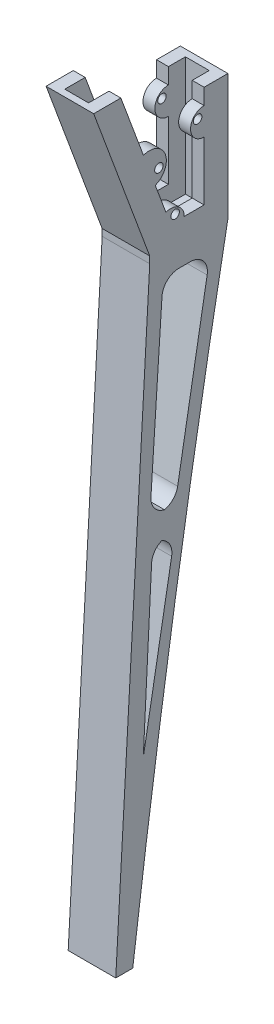
SolidWorks part; units mm, degrees
ref_plane "Front Plane" through (0, 0, 0) normal (0, 0, 1) x (1, 0, 0)
ref_plane "Top Plane" through (0, 0, 0) normal (0, 1, 0) x (1, 0, 0)
ref_plane "Right Plane" through (0, 0, 0) normal (1, 0, 0) x (0, 0, -1)
sketch "Sketch1" plane through (0, 0, 0) normal (0, 1, 0) x (1, 0, 0)
  line L0 (7, 0) -> (10.5, 0)
  line L2 (0, 0) -> (0, 5)
  line L3 (0, 5) -> (7, 5)
  line L4 (7, 0) -> (7, 5)
  line L5 (-3.5, 0) -> (0, 0)
  line L6 (-3.5, 0) -> (-3.5, 7)
  line L7 (-3.5, 7) -> (10.5, 7)
  line L8 (10.5, 0) -> (10.5, 7)
  dimension "D1" = 5
  dimension "D2" = 7
  dimension "D3" = 14
  dimension "D4" = 7
  dimension "D6" = 3.5
extrude "Boss-Extrude1" add sketch "Sketch1" along normal blind 35
sketch "Sketch6" plane through (0, 0, 0) normal (0, -1, 0) x (1, 0, 0)
  line L1 (10.5, -7) -> (-3.5, -7)
  line L2 (10.5, -7) -> (10.5, 16)
  line L3 (10.5, 16) -> (-3.5, 16)
  line L4 (-3.5, -7) -> (-3.5, 16)
  dimension "D1" = 14
  dimension "D2" = 23
extrude "Boss-Extrude6" add sketch "Sketch6" along normal blind 2
sketch "Sketch7" plane through (0, 0, 0) normal (0, 1, 0) x (1, 0, 0)
  line L0 (-3.5, -16) -> (10.5, -16)
  line L1 (10.5, -16) -> (10.5, -8)
  line L2 (10.5, 0) -> (10.5, -16) construction
  line L3 (10.5, -8) -> (7, -8)
  line L4 (7, -8) -> (7, -14)
  line L5 (7, -14) -> (0, -14)
  line L6 (0, -14) -> (0, -8)
  line L7 (0, -8) -> (-3.5, -8)
  line L8 (-3.5, -16) -> (-3.5, 0) construction
  line L9 (-3.5, -8) -> (-3.5, -16)
  dimension "D1" = 2
  dimension "D2" = 8
  dimension "D3" = 7
sketch "Sketch8" plane through (10.5, 0, 0) normal (1, 0, 0) x (0, 0, -1)
  line L2 (-32.5, 44.5) -> (-16, 0)
  dimension "D1" = 16.5
  dimension "D2" = 44.5
sweep "Sweep1" add profiles "Sketch7" path "Sketch8"
sketch "Sketch9" plane through (10.5, 0, 0) normal (1, 0, 0) x (0, 0, -1)
  line L0 (-16, -2) -> (-26, -179)
  line L1 (-16, -2) -> (7, -2)
  line L4 (-5.0833, -7.4335) -> (-12.0833, -7.4335)
  line L5 (-26, -179) -> (-21, -179)
  line L6 (-12.0833, -7.4335) -> (-16, -66.9304)
  line L7 (-5.0833, -7.4335) -> (1.9167, -7.4335)
  line L8 (1.9167, -7.4335) -> (-8.5141, -66.9304)
  line L9 (-8.5141, -66.9304) -> (-16, -66.9304)
  line L10 (-12.2153, -73.8738) -> (-15.2153, -73.8738)
  line L11 (-15.2153, -73.8738) -> (-17.9029, -126.8584)
  line L12 (-17.9029, -126.8584) -> (-8.5141, -73.8738)
  line L13 (-8.5141, -73.8738) -> (-12.2153, -73.8738)
  spline S1 degree 2 poles (7, -2) (-9.6602, -89.8354) (-21, -179) knots 0 0 0 0.8965 0.8965 0.8965
  dimension "D1" = 177
  dimension "D2" = 5
  dimension "D3" = 10
sketch "Sketch13" plane through (10.5, 0, 0) normal (1, 0, 0) x (0, 0, -1)
  line L0 (-8, 0) -> (0, 0)
  line L1 (0, 0) -> (0, 5)
  line L2 (0, 35) -> (0, 0) construction
  line L3 (0, 5) -> (-9.8539, 5)
  line L4 (-24.5, 44.5) -> (-8, 0) construction
  line L5 (-9.8539, 5) -> (-8, 0)
extrude "Boss-Extrude8" add sketch "Sketch13" against normal up to surface (3.5 mm away) up to face at (7, 22.25, 19.25)
sketch "Sketch14" plane through (10.5, 0, 0) normal (1, 0, 0) x (0, 0, -1)
  line L0 (-9.8539, 5) -> (-11.2435, 8.7476)
  line L1 (-24.5, 44.5) -> (-9.8539, 5) construction
  line L2 (-9.8539, 5) -> (-5.8571, 5)
  arc A0 (-5.8571, 5) -> (-11.2435, 8.7476) centre (-9.8539, 5) ccw
  circle A1 centre (-8.532, 6.9) radius 1.25
  dimension "D1" = 1.9
  dimension "D2" = 1.9
extrude "Boss-Extrude9" add sketch "Sketch14" against normal up to surface (14 mm away) up to face at (-3.5, 21.6389, 10.5833)
sketch "Sketch15" plane through (-3.5, 0, 0) normal (-1, 0, 0) x (0, 0, 1)
  line L0 (0, 0) -> (8, 0)
  line L1 (8, 0) -> (9.8539, 5)
  line L2 (9.8539, 5) -> (0, 5)
  line L3 (0, 35) -> (0, 0) construction
  line L4 (0, 5) -> (0, 0)
extrude "Boss-Extrude10" add sketch "Sketch15" against normal up to surface (3.5 mm away) up to face at (0, 17.5, -2.5)
sketch "Sketch16" plane through (10.5, 0, 0) normal (1, 0, 0) x (0, 0, -1)
  line L0 (0, 5) -> (0, 26.3175)
  line L1 (0, 35) -> (0, 5) construction
  line L2 (0, 30.3175) -> (0, 22.3175)
  arc A0 (0, 30.3175) -> (0, 22.3175) centre (0, 26.3175) ccw
  circle A1 centre (-1.9, 27.8175) radius 1.25
  line M1 (0, 35) -> (0, 5)
  dimension "D1" = 1.9
  dimension "D2" = 5.5
extrude "Boss-Extrude11" add sketch "Sketch16" against normal up to surface (14 mm away) contours A0 A1 M1 region at (10.5, 25.9534, 1.6485) up to face at (-3.5, 20.8031, 9.775)
sketch "Sketch18" plane through (10.5, 0, 0) normal (1, 0, 0) x (0, 0, -1)
  line L1 (-24.5, 44.5) -> (-11.2435, 8.7476) construction
  line L3 (-14.3724, 17.1861) -> (-17.8717, 26.6238)
  arc A0 (-14.3724, 17.1861) -> (-17.849, 26.5624) centre (-16.1107, 21.8743) ccw
  circle A1 centre (-13.3107, 21.0743) radius 1.25
  line M6 (-11.2435, 8.7476) -> (-24.5, 44.5)
  dimension "D1" = 0.8
  dimension "D4" = 5
  dimension "D2" = 2.8
  dimension "D3" = 14
extrude "Boss-Extrude12" add sketch "Sketch18" against normal up to surface (14 mm away) contours A0 A1 M6 region at (10.5, 22.8317, 14.2367) up to face at (-3.5, 21.3888, 8.4791)
sketch "Sketch19" plane through (0, 0, 0) normal (0, 1, 0) x (1, 0, 0)
  line L1 (0, -14) -> (7, -14)
  line L2 (0, -14) -> (0, 5)
  line L3 (0, 5) -> (7, 5)
  line L4 (7, -14) -> (7, 5)
extrude "Cut-Extrude5" cut sketch "Sketch19" along normal through all
sketch "Sketch20" plane through (0, -4.5636, 12.3079) normal (0, 0.3477, -0.9376) x (-1, 0, 0)
  line L1 (0, 52.3277) -> (-7, 52.3277)
  line L2 (0, 52.3277) -> (0, 4.8672)
  line L3 (0, 4.8672) -> (-7, 4.8672)
  line L4 (-7, 52.3277) -> (-7, 4.8672)
extrude "Cut-Extrude6" cut sketch "Sketch20" along normal blind 10
extrude "Boss-Extrude13" add sketch "Sketch9" against normal up to surface (14 mm away) up to face at (-3.5, 21.2475, 9.1103)
fillet "Fillet1" radius 5 6 edges at (3.5, -73.8738, 8.5141) (3.5, -73.8738, 15.2153) (3.5, -66.9304, 16) (3.5, -66.9304, 8.5141) (3.5, -7.4335, 12.0833) (3.5, -7.4335, -1.9167)
